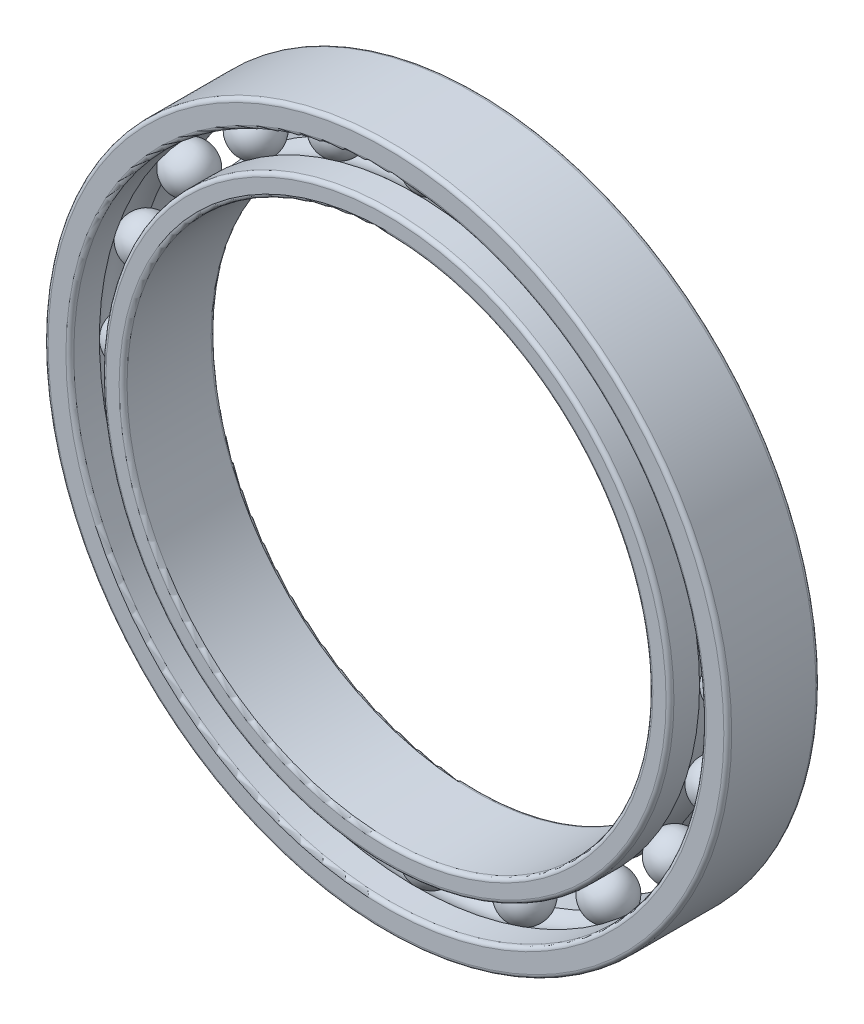
SolidWorks part; units mm, degrees
material "Legierter Stahl"
ref_plane "Ebene vorne" through (0, 0, 0) normal (0, 0, 1) x (1, 0, 0)
ref_plane "Ebene oben" through (0, 0, 0) normal (0, 1, 0) x (1, 0, 0)
ref_plane "Ebene rechts" through (0, 0, 0) normal (1, 0, 0) x (0, 0, -1)
sketch "Skizze1" plane through (0, 0, 0) normal (1, 0, 0) x (0, 0, -1)
  line L0 (0, 0) -> (32.8284, 0) construction
  line L1 (0, 0) -> (0, 22.1569) construction
  line L2 (-3.5, 26) -> (3.5, 26)
  line L3 (3.5, 26) -> (3.5, 24.05)
  line L4 (3.5, 24.05) -> (1.2522, 24.05)
  line L5 (1.2522, 21.605) -> (3.5, 21.605)
  line L6 (3.5, 21.605) -> (3.5, 20)
  line L7 (3.5, 20) -> (-3.5, 20)
  line L8 (-3.5, 21.605) -> (-3.5, 20)
  line L9 (-1.2522, 21.605) -> (-3.5, 21.605)
  line L10 (-3.5, 24.05) -> (-1.2522, 24.05)
  line L11 (-3.5, 26) -> (-3.5, 24.05)
  line L12 (-1.2522, 24.05) -> (0, 22.8275) construction
  line L13 (0, 22.8275) -> (1.2522, 21.605) construction
  line L14 (-1.75, 22.8275) -> (1.75, 22.8275)
  circle A0 centre (0, 22.8275) radius 1.75
  point P17 (0, 20)
  point P22 (0, 26)
  dimension "D1" = 40
  dimension "D6" = 3.5
  dimension "D2" = 52
  dimension "D3" = 7
  dimension "D4" = 43.21
  dimension "D5" = 48.1
revolve "Rotation1" add sketch "Skizze1" angle 360 about L0 region at (0, 25.0794, 0) region at (0, 20.7506, 0)
revolve "Rotation3" add sketch "Skizze1<5>" angle 360 about L14 region at (0, 23.5702, 0)
sketch "Skizze1<5>" plane through (0, 0, 0) normal (1, 0, 0) x (0, 0, -1) same geometry as "Skizze1"
ref_axis "Achse1" through (0, 0, -3.5) along (0, 0, 1)
pattern_circular "Kreismuster4" count 20 over 360 about axis through (0, 0, -3.5) along (0, 0, 1) of bodies 110
fillet "Verrundung1" radius 0.3 4 edges at (24.05, 0, -3.5) (24.05, 0, 3.5) (26, 0, -3.5) (26, 0, 3.5)
fillet "Verrundung2" radius 0.3 4 edges at (21.605, 0, -3.5) (20, 0, -3.5) (21.605, 0, 3.5) (20, 0, 3.5)
